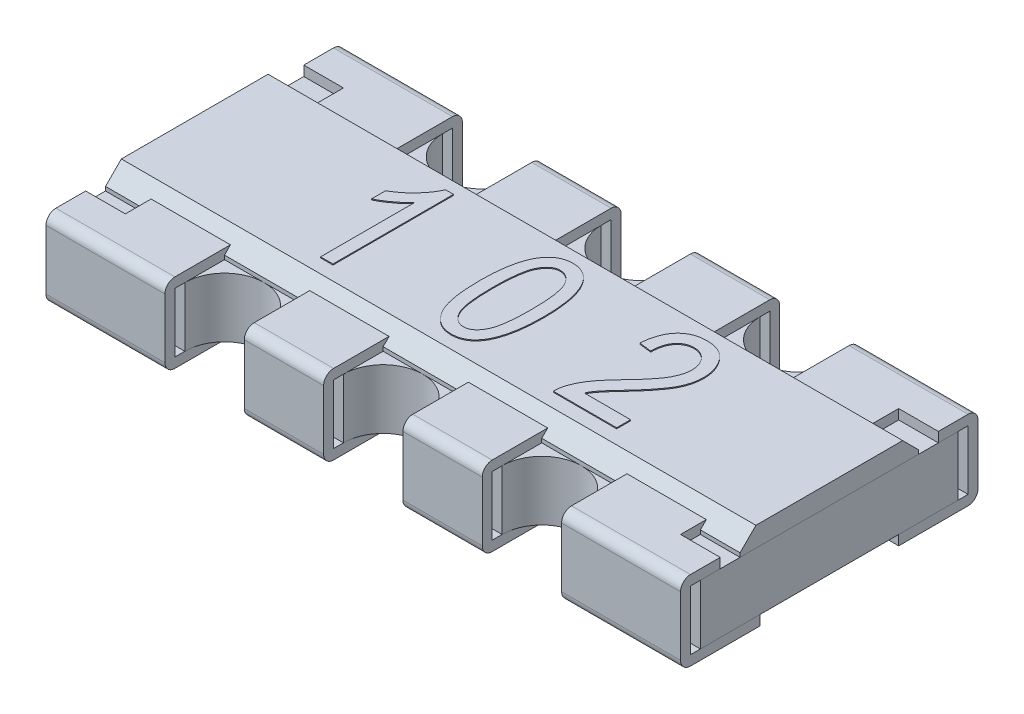
SolidWorks part; units mm, degrees
material "E-Glass Fiber"
ref_plane "Front Plane" through (0, 0, 0) normal (0, 0, 1) x (1, 0, 0)
ref_plane "Top Plane" through (0, 0, 0) normal (0, 1, 0) x (1, 0, 0)
ref_plane "Right Plane" through (0, 0, 0) normal (1, 0, 0) x (0, 0, -1)
sketch "Sketch5" plane through (0, 0, 0) normal (1, 0, 0) x (0, 0, -1)
  line L0 (55, 0) -> (-55, 0) construction
  line L1 (-0.7, 0.4) -> (0.7, 0.4)
  line L2 (-0.75, 0.35) -> (-0.75, 0.05)
  line L3 (-0.7, 0) -> (-0.35, 0)
  line L4 (0.75, 0.35) -> (0.75, 0.05)
  line L5 (0, 55) -> (0, -55) construction
  line L8 (0.35, 0) -> (0.7, 0)
  arc A0 (0.7, 0.4) -> (0.75, 0.35) centre (0.7, 0.35) cw
  arc A1 (0.7, 0) -> (0.75, 0.05) centre (0.7, 0.05) ccw
  arc A2 (-0.75, 0.05) -> (-0.7, 0) centre (-0.7, 0.05) ccw
  arc A3 (-0.7, 0.4) -> (-0.75, 0.35) centre (-0.7, 0.35) ccw
  point P10 (0.75, 0.4)
  point P13 (0.75, 0)
  point P18 (-0.75, 0.4)
  dimension "D4" = 0.05
  dimension "D1" = 0.4
  dimension "D2" = 1.5
  dimension "D3" = 0.75
  dimension "D5" = 0.4
  dimension "D6" = 0.4
extrude "Extrude-Thin1" add sketch "Sketch5" along normal mid plane 3.2 thin thin type one direction reverse wall 0.05
sketch "Sketch6" plane through (0, 0.4, 0) normal (0, 1, 0) x (1, 0, 0)
  line L1 (1.6, 0.75) -> (-1.6, 0.75) construction
  line L2 (-1, 0.75) -> (-0.6, 0.75)
  line L3 (-1, 0.75) -> (-1, 0.25)
  line L4 (-1, 0.25) -> (-0.6, 0.25)
  line L6 (-0.6, 0.75) -> (-0.6, 0.25)
  line L7 (0, -0.22) -> (0, 0.22) construction
  line L8 (-0.2, 0.75) -> (0.2, 0.75)
  line L9 (-0.2, 0.75) -> (-0.2, 0.25)
  line L10 (-0.2, 0.25) -> (0.2, 0.25)
  line L11 (0.2, 0.75) -> (0.2, 0.25)
  line L12 (0.6, 0.75) -> (1, 0.75)
  line L13 (0.6, 0.75) -> (0.6, 0.25)
  line L14 (0.6, 0.25) -> (1, 0.25)
  line L15 (1, 0.75) -> (1, 0.25)
  line L16 (1.6, 0.7) -> (1.6, -0.7) construction
  line L18 (1.6, -0.75) -> (-1.6, -0.75) construction
  line L19 (-1, -0.75) -> (-0.6, -0.75)
  line L20 (-1, -0.75) -> (-1, -0.25)
  line L21 (-1, -0.25) -> (-0.6, -0.25)
  line L22 (-0.6, -0.75) -> (-0.6, -0.25)
  line L24 (-0.2, -0.75) -> (0.2, -0.75)
  line L25 (-0.2, -0.75) -> (-0.2, -0.25)
  line L26 (-0.2, -0.25) -> (0.2, -0.25)
  line L27 (0.2, -0.75) -> (0.2, -0.25)
  line L28 (0.6, -0.75) -> (1, -0.75)
  line L29 (0.6, -0.75) -> (0.6, -0.25)
  line L30 (0.6, -0.25) -> (1, -0.25)
  line L31 (1, -0.75) -> (1, -0.25)
  dimension "D1" = 0.5
  dimension "D2" = 0.4
  dimension "D3" = 0.8
  dimension "D4" = 0.2
  dimension "D5" = 0.8
  dimension "D6" = 0.4
  dimension "D7" = 0.4
  dimension "D8" = 0.6
extrude "Cut-Extrude3" cut sketch "Sketch6" against normal through all
sketch "Sketch7" plane through (0, 0.4, 0) normal (0, 1, 0) x (1, 0, 0)
  line L0 (-1.6, 0.7) -> (-1.6, -0.7) construction
  line L1 (-1.6, -0.55) -> (-1.4, -0.55)
  line L2 (-1.6, -0.55) -> (-1.6, 0.55)
  line L3 (-1.6, 0.55) -> (-1.4, 0.55)
  line L4 (-1.4, -0.55) -> (-1.4, 0.55)
  line L5 (1.6, 0.7) -> (1.6, -0.7) construction
  line L6 (1.6, -0.55) -> (1.4, -0.55)
  line L7 (1.6, -0.55) -> (1.6, 0.55)
  line L8 (1.6, 0.55) -> (1.4, 0.55)
  line L9 (1.4, -0.55) -> (1.4, 0.55)
  line L12 (-0.22, 0) -> (0.22, 0) construction
  dimension "D1" = 0.55
  dimension "D2" = 1.1
  dimension "D3" = 0.2
extrude "Cut-Extrude4" cut sketch "Sketch7" against normal blind 0.1
sketch "Sketch1" plane through (0, 0.05, 0) normal (0, 1, 0) x (1, 0, 0)
  line L0 (-1.6, -0.65) -> (1.6, 0.65) construction
  line L1 (-1.6, 0.65) -> (1.6, 0.65)
  line L2 (-1.6, 0.65) -> (-1.6, -0.65)
  line L3 (-1.6, -0.65) -> (1.6, -0.65)
  line L4 (1.6, 0.65) -> (1.6, -0.65)
  line L5 (-1.2, 0.65) -> (-1.2, -0.65) construction
  line L6 (-1.6, 0.45) -> (1.6, 0.45) construction
  line L7 (-0.4, 0.65) -> (-0.4, -0.65) construction
  line L8 (-1.6, -0.45) -> (1.6, -0.45) construction
  line L9 (0.4, 0.65) -> (0.4, -0.65) construction
  line L10 (0, -0.22) -> (0, 0.22) construction
  line L11 (1.2, 0.65) -> (1.2, -0.65) construction
  dimension "D3" = 0.2
  dimension "D1" = 3.2
  dimension "D2" = 1.3
  dimension "D4" = 0.2
  dimension "D5" = 0.8
  dimension "D6" = 0.8
  dimension "D7" = 0.8
  dimension "D8" = 0.4
extrude "Boss-Extrude3" add sketch "Sketch1" along normal blind 0.3 separate body
sketch "Sketch9" plane through (0, 0.35, 0) normal (0, 1, 0) x (1, 0, 0)
  line L1 (-1.6, 0.45) -> (1.6, 0.45)
  line L2 (-1.6, 0.45) -> (-1.6, -0.45)
  line L3 (-1.6, -0.45) -> (1.6, -0.45)
  line L4 (1.6, 0.45) -> (1.6, -0.45)
extrude "Boss-Extrude4" add sketch "Sketch9" along normal blind 0.1
chamfer "Chamfer1" distance 0.08 angle 45 2 edges at (0, 0.45, 0.45) (0, 0.45, -0.45)
sketch "Sketch10" plane through (0, 0.05, 0) normal (0, 1, 0) x (1, 0, 0)
  line L0 (-1.6, 0.65) -> (1.6, 0.65) construction
  line L1 (-1.6, -0.65) -> (1.6, -0.65) construction
  line L2 (0, -0.2475) -> (0, 0.2475) construction
  circle A0 centre (-0.8, 0.65) radius 0.2
  circle A1 centre (0, 0.65) radius 0.2
  circle A2 centre (0.8, 0.65) radius 0.2
  circle A3 centre (0.8, -0.65) radius 0.2
  circle A4 centre (0, -0.65) radius 0.2
  circle A5 centre (-0.8, -0.65) radius 0.2
  dimension "D3" = 0.4
  dimension "D1" = 0.8
  dimension "D2" = 0.8
extrude "Cut-Extrude7" cut sketch "Sketch10" along normal blind 5
sketch "Sketch11" plane through (0, 0.45, 0) normal (0, 1, 0) x (1, 0, 0)
  line L0 (0, -0.2475) -> (0, 0.2475) construction
  line L2 (-0.2475, 0) -> (0.2475, 0) construction
  text T0 "1 0 2" font "Arial Narrow" height 0.6
  dimension "D1" = 0.86
  dimension "D2" = 0.3
extrude "Boss-Extrude5" add sketch "Sketch11" along normal blind 0.005
ref_plane "Plane1" through (-1.2, 0, 0) normal (1, 0, 0) x (0, 0, -1)
